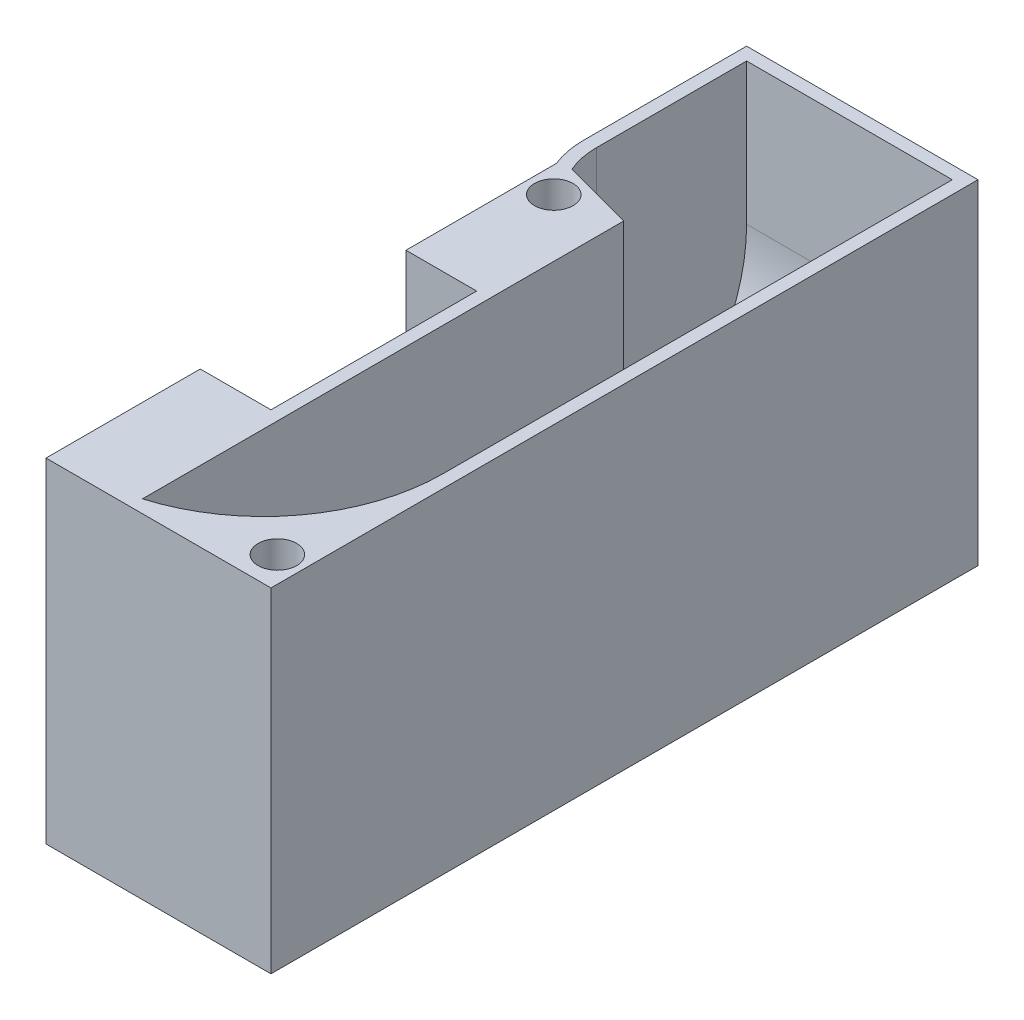
SolidWorks part; units mm, degrees
ref_plane "Front Plane" through (0, 0, 0) normal (0, 0, 1) x (1, 0, 0)
ref_plane "Top Plane" through (0, 0, 0) normal (0, 1, 0) x (1, 0, 0)
ref_plane "Right Plane" through (0, 0, 0) normal (1, 0, 0) x (0, 0, -1)
sketch "Sketch2" plane through (0, 0, 0) normal (0, -1, 0) x (1, 0, 0)
  line L0 (0, 0) -> (13, 0) construction
  line L18 (7.5, -8) -> (7.5, -19.7113)
  line L19 (7, -22.3094) -> (7, -35)
  line L20 (7, -35) -> (25, -35)
  line L21 (25, -35) -> (25, 20)
  line L22 (25, 20) -> (7.5, 20)
  line L23 (7.5, 20) -> (7.5, 8)
  line L24 (7.5, 8) -> (13, 8)
  line L25 (13, 8) -> (13, -8)
  line L26 (13, -8) -> (7.5, -8)
  arc A2 (7.5, -19.7113) -> (7, -22.3094) centre (14, -22.3094) ccw
  dimension "D8" = 7
  dimension "D1" = 13
  dimension "D2" = 16
  dimension "D3" = 5.5
  dimension "D4" = 20
  dimension "D5" = 17.5
  dimension "D6" = 55
  dimension "D7" = 7
  dimension "D9" = 12.6906
extrude "Boss-Extrude2" add sketch "Sketch2" along normal blind 26 separate body
shell "Shell1" thickness 1 removed face at (11.9876, 0, -7.1997)
fillet "Fillet1" radius 14 1 edges at (16, -25, -34)
sketch "Sketch3" plane through (0, 0, 0) normal (0, 1, 0) x (1, 0, 0)
  line L0 (14, 9) -> (8.5, 9)
  line L1 (8.5, 9) -> (8.5, 19.9115)
  line L2 (8.5, 19.9115) -> (14, 18.4378)
  line L3 (14, 18.4378) -> (14, 9)
  line L5 (14, -9) -> (8.5, -9)
  line L6 (14, -9) -> (14, -19)
  line L7 (14, -19) -> (8.5, -19)
  line L8 (8.5, -9) -> (8.5, -19)
  line L9 (11.25, -19) -> (11.25, -9) construction
  line L10 (14, -14) -> (8.5, -14) construction
  point P139 (11.25, -14)
  dimension "D1" = 75
extrude "Boss-Extrude3" add sketch "Sketch3" against normal up to next
sketch "Sketch4" plane through (7.5, 0, 0) normal (-1, 0, 0) x (0, 0, 1)
  line L0 (11.5, -23) -> (-11.5, -23) construction
  line L1 (0, 0) -> (0, -23) construction
  line L4 (8, -26) -> (-8, -26) construction
  circle A0 centre (-11.5, -23) radius 2
  circle A1 centre (11.5, -23) radius 2
  dimension "D1" = 4
  dimension "D2" = 23
  dimension "D3" = 3
extrude "Cut-Extrude1" cut sketch "Sketch4" against normal up to surface (6.5 mm away)
fillet "Fillet2" radius 14 1 edges at (24, -12.5, 19)
sketch "Sketch7" plane through (0, 0, 0) normal (0, 1, 0) x (1, 0, 0)
  line L0 (9.5, 17.5) -> (9.5, -17.5) construction
  line L1 (9.5, -17.5) -> (23, -17.5) construction
  line L2 (0, 0) -> (9.5, 0) construction
  circle A0 centre (23, -17.5) radius 1.5
  circle A1 centre (9.5, 17.5) radius 1.5
  dimension "D4" = 3
  dimension "D1" = 9.5
  dimension "D2" = 35
  dimension "D3" = 13.5
extrude "Cut-Extrude2" cut sketch "Sketch7" against normal blind 3
